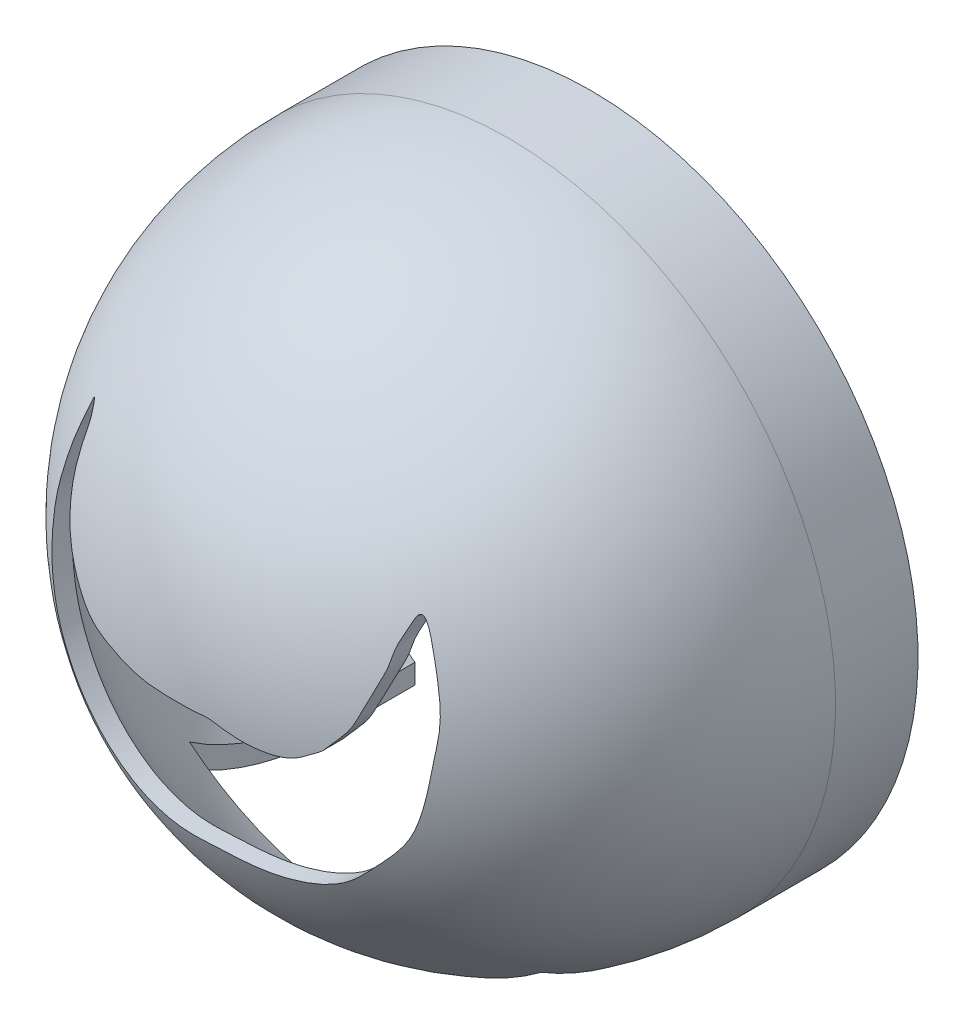
SolidWorks part; units mm, degrees
ref_plane "Front Plane" through (0, 0, 0) normal (0, 0, 1) x (1, 0, 0)
ref_plane "Top Plane" through (0, 0, 0) normal (0, 1, 0) x (1, 0, 0)
ref_plane "Right Plane" through (0, 0, 0) normal (1, 0, 0) x (0, 0, -1)
sketch "Sketch2" plane through (0, 0, 0) normal (1, 0, 0) x (0, 0, -1)
  line L7 (76.0803, 0) -> (147.5803, 0)
  line L8 (147.5803, 0) -> (147.5803, 56.5)
  line L9 (147.5803, 56.5) -> (132.5803, 56.5)
  line L10 (132.5803, 56.5) -> (132.5803, 0) construction
  line L11 (76.0803, 0) -> (46.7658, 0) construction
  arc A1 (132.5803, 56.5) -> (76.0803, 0) centre (132.5803, 0) ccw
  dimension "D4" = 56.5
  dimension "D3" = 15
sketch "Sketch3" plane through (0, 0, 0) normal (0, 0, 1) x (1, 0, 0)
  line L0 (34.4527, 94.4567) -> (335.1193, 94.4567) construction
  line L1 (0, 25) -> (0, -25) construction
  line L2 (35, 25) -> (-35, 25) construction
  line L3 (35, 25) -> (35, -25) construction
  line L4 (35, -25) -> (-35, -25) construction
  line L5 (-35, 25) -> (-35, -25) construction
  line L6 (35, 0) -> (-35, 0) construction
  spline S0 degree 3 poles (29.575, 21.7034) (29.1589, 20.0607) (28.4458, 18.5092) (28.357, 15.5515) (27.3739, 12.2639) (26.2779, 9.0024) (24.868, 5.1665) (23.0392, 3.3242) (21.6495, 1.39) (20.0507, 0.4881) (18.4016, -0.7646) (15.7758, -1.5543) (13.0817, -1.5226) (9.8677, -1.2145) (7.1538, -0.4984) (4.4783, 0.2669) (2.4011, 0.0337) (-0.2247, 0.1089) (-4.0632, -0.0696) (-7.7729, -0.0822) (-11.3773, 0.3499) (-15.0052, 0.9536) (-19.6326, 1.437) (-23.9939, 4.4987) (-28.2468, 8.6969) (-30.6536, 14.9638) (-30.274, 20.3176) (-30.1494, 23.4752) (-31.3551, 25.582) (-31.5859, 24.3813) (-32.1162, 22.2568) (-33.2944, 18.7717) (-34.0389, 14.3887) (-34.8909, 10.4441) (-35.0476, 7.3221) (-34.8929, 3.6195) (-34.4734, -2.24) (-33.1374, -8.7935) (-26.9111, -16.6873) (-20.857, -21.836) (-13.3086, -24.8322) (-5.6918, -25.5706) (1.1197, -24.1892) (10.2666, -25.0194) (20.2657, -23.6349) (26.6936, -16.4382) (31.4427, -11.5699) (33.9933, -3.849) (34.6467, 2.5093) (35.1921, 7.7169) (34.3684, 14.2138) (30.3059, 24.6879) (29.575, 21.7034) (29.1589, 20.0607) (28.4458, 18.5092) knots -0.036948 -0.002347 -0.000235 0 0.018272 0.027174 0.035831 0.061861 0.070881 0.08706 0.094196 0.100655 0.109984 0.120337 0.134591 0.143877 0.161163 0.170165 0.178714 0.187249 0.203727 0.225194 0.236365 0.249274 0.272052 0.293932 0.315061 0.347273 0.37546 0.380218 0.390051 0.393573 0.398559 0.416614 0.441035 0.4544 0.467622 0.480754 0.501005 0.540881 0.57479 0.610262 0.644508 0.675425 0.704128 0.732237 0.792286 0.820872 0.851803 0.879325 0.914057 0.933556 0.963052 0.997653 0.999765 1 1.018272 1.027174 1.035831 only from (29.5229, 21.4978) to (29.5229, 21.4978)
  dimension "D1" = 50
  dimension "D2" = 70
  dimension "D3" = 25
revolve "Revolve1" add sketch "Sketch2" angle 360 about L11
shell "Shell1" thickness 3 removed face at (-56.5, 0, -147.5803) outward yes
extrude "Cut-Extrude1" cut sketch "Sketch3" against normal through all
sketch "Sketch4" plane through (0, 0, 0) normal (0, 1, 0) x (1, 0, 0)
  line L0 (59.5, 147.5803) -> (-59.5, 147.5803) construction
  line L1 (59.5, 147.5803) -> (-59.5, 147.5803) construction
  line L2 (0, 147.5803) -> (0, 105.8447) construction
  line L4 (-32, 147.5803) -> (32, 147.5803)
  line L5 (-32, 147.5803) -> (-32, 106.5803)
  line L6 (-32, 106.5803) -> (32, 106.5803)
  line L7 (32, 147.5803) -> (32, 106.5803)
  point P9 (0, 147.5803)
  dimension "D1" = 64
  dimension "D2" = 41
extrude "Cut-Extrude2" cut sketch "Sketch4" against normal through all
